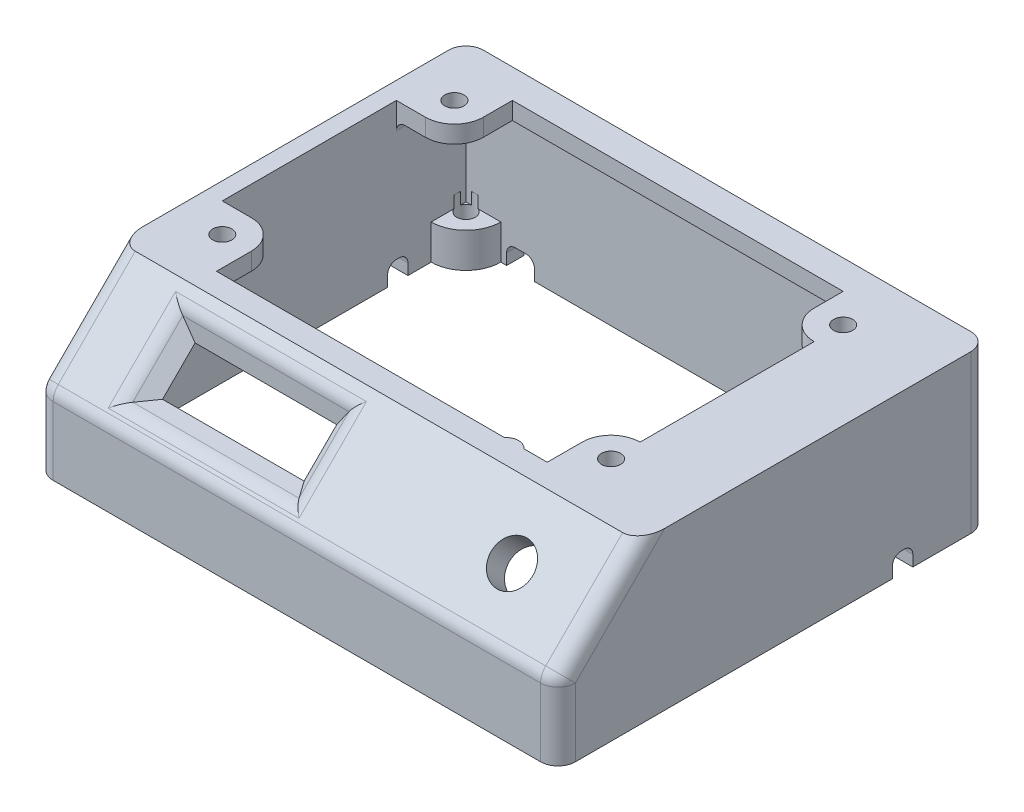
SolidWorks part; units mm, degrees
ref_plane "Front Plane" through (0, 0, 0) normal (0, 0, 1) x (1, 0, 0)
ref_plane "Top Plane" through (0, 0, 0) normal (0, 1, 0) x (1, 0, 0)
ref_plane "Right Plane" through (0, 0, 0) normal (1, 0, 0) x (0, 0, -1)
sketch "Sketch1" plane through (0, 0, 0) normal (0, 1, 0) x (1, 0, 0)
  line L1 (-45, 30) -> (45, 30)
  line L2 (-45, 30) -> (-45, -30)
  line L3 (-45, -30) -> (45, -30)
  line L4 (45, 30) -> (45, -30)
  line L5 (-45, 30) -> (45, -30) construction
  line L6 (-45, -30) -> (45, 30) construction
  point P0 (0, 0)
  dimension "D1" = 60
  dimension "D2" = 90
extrude "Boss-Extrude1" add sketch "Sketch1" along normal blind 3
ref_plane "Plane1" through (0, 16.5, 16.5) normal (0, 0.7071, 0.7071) x (1, 0, 0)
sketch "Sketch3" plane through (0, 16.5, 16.5) normal (0, 0.7071, 0.7071) x (1, 0, 0)
  line L1 (-45, -19.0919) -> (45, -19.0919)
  line L2 (-45, -19.0919) -> (-45, -39.0919)
  line L3 (-45, -39.0919) -> (45, -39.0919)
  line L4 (45, -19.0919) -> (45, -39.0919)
  point P5 (0, 0)
  point P6 (0, 0)
  dimension "D1" = 20
extrude "Boss-Extrude2" add sketch "Sketch3" against normal blind 3
sketch "Sketch4" plane through (0, 16.5, 16.5) normal (0, 0.7071, 0.7071) x (1, 0, 0)
  line L0 (-45, -19.0919) -> (45, -19.0919) construction
  line L1 (45, -39.0919) -> (45, -19.0919) construction
  circle A0 centre (30, -29.0919) radius 3.6
  dimension "D1" = 7.2
  dimension "D2" = 10
  dimension "D3" = 15
extrude "Cut-Extrude1" cut sketch "Sketch4" against normal up to surface (3 mm away) up to face at (0, -6.6317, 35.3891)
sketch "Sketch5" plane through (0, 14.3787, 14.3787) normal (0, -0.7071, -0.7071) x (1, 0, 0)
  circle A0 centre (30, 29.0919) radius 5.5
  circle A1 centre (30, 29.0919) radius 3.6
  dimension "D1" = 11
extrude "Boss-Extrude3" add sketch "Sketch5" along normal up to surface (1.4 mm away)
sketch "Sketch6" plane through (0, 16.5, 16.5) normal (0, 0.7071, 0.7071) x (1, 0, 0)
  line L0 (-29.3386, -25.3219) -> (-29.3386, -32.8619) construction
  line L1 (-29.3386, -25.3219) -> (-5.3386, -25.3219)
  line L2 (-29.3386, -25.3219) -> (-29.3386, -32.8619)
  line L3 (-29.3386, -32.8619) -> (-5.3386, -32.8619)
  line L4 (-5.3386, -25.3219) -> (-5.3386, -32.8619)
  line L5 (-29.3386, -32.8619) -> (-5.3386, -32.8619) construction
  line L6 (-5.3386, -32.8619) -> (-5.3386, -25.3219) construction
  line L7 (-5.3386, -25.3219) -> (-29.3386, -25.3219) construction
extrude "Cut-Extrude2" cut sketch "Sketch6" against normal up to surface (3 mm away) up to face at (0, -6.6317, 35.3891)
chamfer "Chamfer1" distance 3.2 angle 45 4 edges at (-5.3386, -4.0711, 37.0711) (-17.3386, -6.7369, 39.7369) (-17.3386, -1.4053, 34.4053) (-29.3386, -4.0711, 37.0711)
sketch "Sketch7" plane through (0, 14.3787, 14.3787) normal (0, -0.7071, -0.7071) x (1, 0, 0)
  circle A0 centre (19.29, 20.8419) radius 3
  circle A2 centre (19.29, 20.8419) radius 1.6
  arc A4 (20.2295, 21.9463) -> (19.5837, 19.4219) centre (19.29, 20.8419) ccw construction
  dimension "D2" = 3.2
extrude "Boss-Extrude4" add sketch "Sketch7" along normal up to surface (8.3 mm away)
sketch "Sketch8" plane through (0, 14.3787, 14.3787) normal (0, -0.7071, -0.7071) x (1, 0, 0)
  line L13 (-35.5386, 36.0719) -> (-35.5386, 23.8719)
  line L14 (-35.5386, 23.8719) -> (2.6614, 23.8719)
  line L15 (2.6614, 23.8719) -> (2.6614, 36.0719)
  line L16 (2.6614, 36.0719) -> (-35.5386, 36.0719)
  line L18 (-35.5386, 23.8719) -> (2.6614, 23.8719)
  line L19 (2.6614, 23.8719) -> (2.6614, 36.0719)
  line L20 (2.6614, 36.0719) -> (-35.5386, 36.0719)
  line L21 (-35.5386, 23.8719) -> (-35.5386, 20.9719)
  line L22 (-35.5386, 36.0719) -> (-35.5386, 38.9719)
  line L25 (-38.4386, 38.9719) -> (-38.4386, 20.9719)
  line L26 (-38.4386, 20.9719) -> (5.5614, 20.9719)
  line L27 (5.5614, 20.9719) -> (5.5614, 38.9719)
  line L28 (5.5614, 38.9719) -> (-38.4386, 38.9719)
  line L30 (-35.5386, 20.9719) -> (5.5614, 20.9719)
  line L31 (5.5614, 20.9719) -> (5.5614, 38.9719)
  line L32 (5.5614, 38.9719) -> (-35.5386, 38.9719)
  dimension "D1" = 0.1
  dimension "D2" = 3
extrude "Boss-Extrude5" add sketch "Sketch8" along normal blind 4
ref_plane "Plane2" through (0, 0, 44.1421) normal (0, 0, 1) x (1, 0, 0)
sketch "Sketch9" plane through (0, 0, 44.1421) normal (0, 0, 1) x (1, 0, 0)
  line L0 (-45, -11.1421) -> (45, -11.1421) construction
  line L1 (-45, -11.1421) -> (45, -11.1421)
  line L2 (-45, -11.1421) -> (-45, -24.1421)
  line L3 (-45, -24.1421) -> (45, -24.1421)
  line L4 (45, -11.1421) -> (45, -24.1421)
  point P6 (0, 0)
  dimension "D1" = 13
extrude "Boss-Extrude6" add sketch "Sketch9" against normal blind 3
sketch "Sketch10" plane through (45, 0, 0) normal (1, 0, 0) x (0, 0, -1)
  line L0 (-28.7574, 0) -> (30, 0) construction
  line L1 (-41.1421, -24.1421) -> (-41.1421, -12.3848) construction
  line L2 (-41.1421, -12.3848) -> (-28.7574, 0) construction
  line L3 (-28.7574, 0) -> (30, 0)
  line L4 (-41.1421, -24.1421) -> (-41.1421, -12.3848)
  line L5 (-41.1421, -12.3848) -> (-28.7574, 0)
  line L6 (-41.1421, -24.1421) -> (30, -24.1421)
  line L7 (30, 0) -> (30, -24.1421)
  point P4 (0, 0)
extrude "Boss-Extrude7" add sketch "Sketch10" against normal blind 3
mirror "Mirror1" about plane through (0, 0, 0) normal (1, 0, 0) of "Boss-Extrude7"
sketch "Sketch11" plane through (0, 0, -30) normal (0, 0, -1) x (-1, 0, 0)
  line L1 (42, -24.1421) -> (-42, -24.1421)
  line L2 (42, -24.1421) -> (42, 0)
  line L3 (42, 0) -> (-42, 0)
  line L4 (-42, -24.1421) -> (-42, 0)
extrude "Boss-Extrude8" add sketch "Sketch11" against normal blind 3
hole_wizard "Ø3.0mm Dowel Hole1" positions "Sketch13" profile "Sketch14" hole size "Ø3.0" standard "ANSI Metric" end condition through all
sketch "Sketch13" plane through (0, 0, 0) normal (0, -1, 0) x (-1, 0, 0)
  line L0 (-45, 30) -> (45, 30) construction
  line L3 (-45, -30) -> (-45, 30) construction
  line L4 (45, 30) -> (45, -30) construction
  point P0 (37, 20)
  point P2 (37, -20)
  point P4 (-30, 20)
  point P6 (-30, -20)
  point P15 (34.9468, 15.9898)
  point P18 (0, 0)
  point P19 (0, 0)
  point P20 (0, 0)
  point P25 (0, 0)
  point P28 (-30, -6.3368)
  point P29 (-30, -14.1656)
  point P30 (0, 0)
  dimension "D1" = 10
  dimension "D2" = 40
  dimension "D3" = 8
  dimension "D4" = 15
sketch "Sketch14" plane through (-37, 0, -20) normal (1, 0, 0) x (0, 0, -1)
  line L0 (0, 0) -> (0, 3)
  line L1 (0, 3) -> (1.65, 3)
  line L2 (1.65, 3) -> (1.65, 0)
  line L5 (1.65, 0) -> (0, 0)
  line L11 (0, -6.35) -> (0, 107.95) construction
  dimension "Thru Hole Dia." = 3.3
  dimension "Thru Hole Depth" = 3
sketch "Sketch15" plane through (0, 0, 0) normal (0, -1, 0) x (-1, 0, 0)
  line L0 (-25, 20) -> (-25, 25)
  line L2 (32, 20) -> (32, 25)
  line L3 (37, 15) -> (42, 15)
  line L4 (37, -15) -> (42, -15)
  line L5 (42, 27) -> (-42, 27)
  line L6 (-42, 27) -> (-42, -28.7574)
  line L7 (-42, -28.7574) -> (-22.2468, -28.7574)
  line L8 (-16.3332, -28.7574) -> (42, -28.7574)
  line L9 (42, -28.7574) -> (42, 27)
  line L14 (42, -15) -> (42, 15)
  line L15 (32, -20) -> (32, -26)
  line L17 (-25, -20) -> (-25, -26)
  line L21 (-25, -26) -> (-21.0112, -26)
  line L22 (45, -30) -> (-45, -30) construction
  line L23 (-17.5688, -26) -> (32, -26)
  line L24 (-25, 25) -> (32, 25)
  line L25 (-45, 30) -> (45, 30) construction
  line L26 (-30, -15) -> (-30, 15)
  arc A0 (32, 20) -> (37, 15) centre (37, 20) ccw
  arc A1 (37, -15) -> (32, -20) centre (37, -20) ccw
  arc A3 (-25, -20) -> (-30, -15) centre (-30, -20) ccw
  arc A4 (-30, 15) -> (-25, 20) centre (-30, 20) ccw
  ellipse E1 centre (-19.29, -29.4749) end of major axis (-19.29, -33.7175) minor radius 3 (-16.3332, -28.7574) -> (-22.2468, -28.7574) ccw
  ellipse E2 centre (-19.29, -29.4749) end of major axis (-19.29, -33.7175) minor radius 3 (-17.5688, -26) -> (-21.0112, -26) ccw
  dimension "D2" = 5
  dimension "D3" = 4
  dimension "D4" = 5
  dimension "D1" = 0
extrude "Cut-Extrude3" cut sketch "Sketch15" against normal up to surface (3 mm away) up to face at (-37, 3, -21.65)
sketch "Sketch16" plane through (0, -24.1421, 0) normal (0, -1, 0) x (-1, 0, 0)
  line L0 (42, -41.1421) -> (-42, -41.1421) construction
  line L1 (42, -41.1421) -> (42, 27) construction
  line L2 (-42, 27) -> (42, 27) construction
  line L3 (-42, -41.1421) -> (-42, 27) construction
  line L4 (42, -41.1421) -> (36, -41.1421)
  line L5 (42, -41.1421) -> (42, -35.1421)
  line L6 (-42, 27) -> (-36, 27)
  line L7 (-42, -41.1421) -> (-42, -35.1421)
  line L8 (-42, 21) -> (-42, 27)
  line L9 (-36, -41.1421) -> (-42, -41.1421)
  line L10 (36, 27) -> (42, 27)
  line L11 (42, 21) -> (42, 27)
  arc A0 (-42, 21) -> (-36, 27) centre (-42, 27) ccw
  arc A1 (-36, -41.1421) -> (-42, -35.1421) centre (-42, -41.1421) ccw
  arc A2 (36, 27) -> (42, 21) centre (42, 27) ccw
  arc A3 (42, -35.1421) -> (36, -41.1421) centre (42, -41.1421) ccw
  dimension "D1" = 6
extrude "Boss-Extrude9" add sketch "Sketch16" against normal blind 6
hole_wizard "Ø1.0mm Dowel Hole1" positions "Sketch17" profile "Sketch19" hole size "Ø1.0" standard "ANSI Metric"
sketch "Sketch17" plane through (0, -24.1421, 0) normal (0, -1, 0) x (-1, 0, 0)
  point P0 (-40.5, -39.6421)
  point P3 (-40.5, 25.5)
  point P6 (40.5, 25.5)
  point P9 (40.5, -39.6421)
sketch "Sketch19" plane through (40.5, -24.1421, 39.6421) normal (1, 0, 0) x (0, 0, -1)
  line L0 (0, 0) -> (0, 8.9614)
  line L1 (0, 8.9614) -> (1.6, 8)
  line L2 (1.6, 8) -> (1.6, 0)
  line L5 (1.6, 0) -> (0, 0)
  line L10 (0, 8.9614) -> (-1.6, 8) construction
  line L11 (0, -6.35) -> (0, 107.95) construction
  dimension "Hole Dia." = 3.2
  dimension "Hole Depth" = 8
  dimension "Drill Angle" = 118
fillet "Fillet1" radius 3 11 edges at (-45, -10.5711, -30) (45, -10.5711, -30) (45, -17.6421, 44.1421) (0, -11.1421, 44.1421) (-45, -17.6421, 44.1421) (-32.5386, -4.0711, 37.0711) (-17.3386, -8.9996, 41.9996) (-2.1386, -4.0711, 37.0711) (-17.3386, 0.8575, 32.1425) (-45, -4.0711, 37.0711) (45, -4.0711, 37.0711)
sketch "Sketch20" plane through (0, -24.1421, 0) normal (0, -1, 0) x (-1, 0, 0)
  line L0 (-45, 27) -> (-45, -41.1421) construction
  line L1 (-45, 17) -> (-42, 17)
  line L2 (-45, 17) -> (-45, 13.5)
  line L3 (-45, 13.5) -> (-42, 13.5)
  line L4 (-42, 17) -> (-42, 13.5)
  line L5 (-42, -35.1421) -> (-42, 21) construction
  line L6 (42, 30) -> (-42, 30) construction
  line L7 (30.2, 30) -> (35, 30)
  line L8 (30.2, 30) -> (30.2, 27)
  line L9 (30.2, 27) -> (35, 27)
  line L10 (35, 30) -> (35, 27)
  line L11 (-36, 27) -> (36, 27) construction
  line L12 (42, -35.1421) -> (42, 21) construction
  line L13 (42, 17) -> (45, 17)
  line L14 (42, 17) -> (42, 13.5)
  line L15 (42, 13.5) -> (45, 13.5)
  line L16 (45, 17) -> (45, 13.5)
  line L17 (45, 27) -> (45, -41.1421) construction
  dimension "D1" = 3.5
  dimension "D2" = 3.5
  dimension "D3" = 13
  dimension "D4" = 4.8
  dimension "D5" = 10
extrude "Cut-Extrude4" cut sketch "Sketch20" against normal blind 3.4
fillet "Fillet2" radius 1.5 14 edges at (30, -10.0815, 38.8388) (-42, 0, 21.8787) (-42, 0, -21) (0, 0, -27) (42, 0, 0.8787) (32.1234, 0, 28.7574) (-12.8334, 0, 28.7574) (19.29, -2.4801, 31.2374) (-43.5, -20.7421, -13.5) (-43.5, -20.7421, -17) (-30.2, -20.7421, -28.5) (-35, -20.7421, -28.5) (43.5, -20.7421, -13.5) (43.5, -20.7421, -17)
chamfer "Chamfer2" distance 2.8 angle 45 3 edges at (-14.9886, -3.2791, 26.3796) (-14.9886, -16.007, 39.1075) (5.5614, -9.6431, 32.7436)
